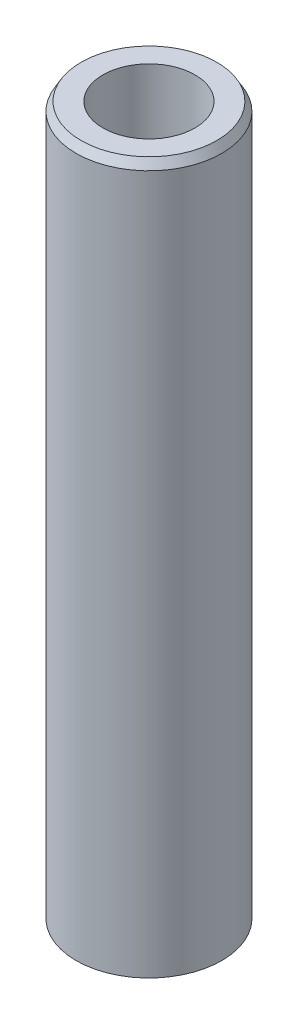
SolidWorks part; units mm, degrees
ref_plane "Front Plane" through (0, 0, 0) normal (0, 0, 1) x (1, 0, 0)
ref_plane "Top Plane" through (0, 0, 0) normal (0, 1, 0) x (1, 0, 0)
ref_plane "Right Plane" through (0, 0, 0) normal (1, 0, 0) x (0, 0, -1)
sketch "Sketch1" plane through (0, 0, 0) normal (0, 1, 0) x (1, 0, 0)
  circle A0 centre (0, 0) radius 7.5
  dimension "SHAFT_OD" = 15
extrude "Boss-Extrude1" add sketch "Sketch1" along normal blind 73.3791
sketch "Sketch2" plane through (0, 0, 0) normal (0, 1, 0) x (1, 0, 0)
  circle A0 centre (0, 0) radius 4.7403
  dimension "BORE_D" = 9.4806
extrude "Cut-Extrude1" cut sketch "Sketch2" along normal through all
chamfer "Chamfer1" distance 0.8882 angle 30 2 edges at (0, 73.3791, 7.5) (0, 0, 7.5) first distance on face at (0, 73.3791, 7.5) first distance on face at (0, 0, 4.7403)
